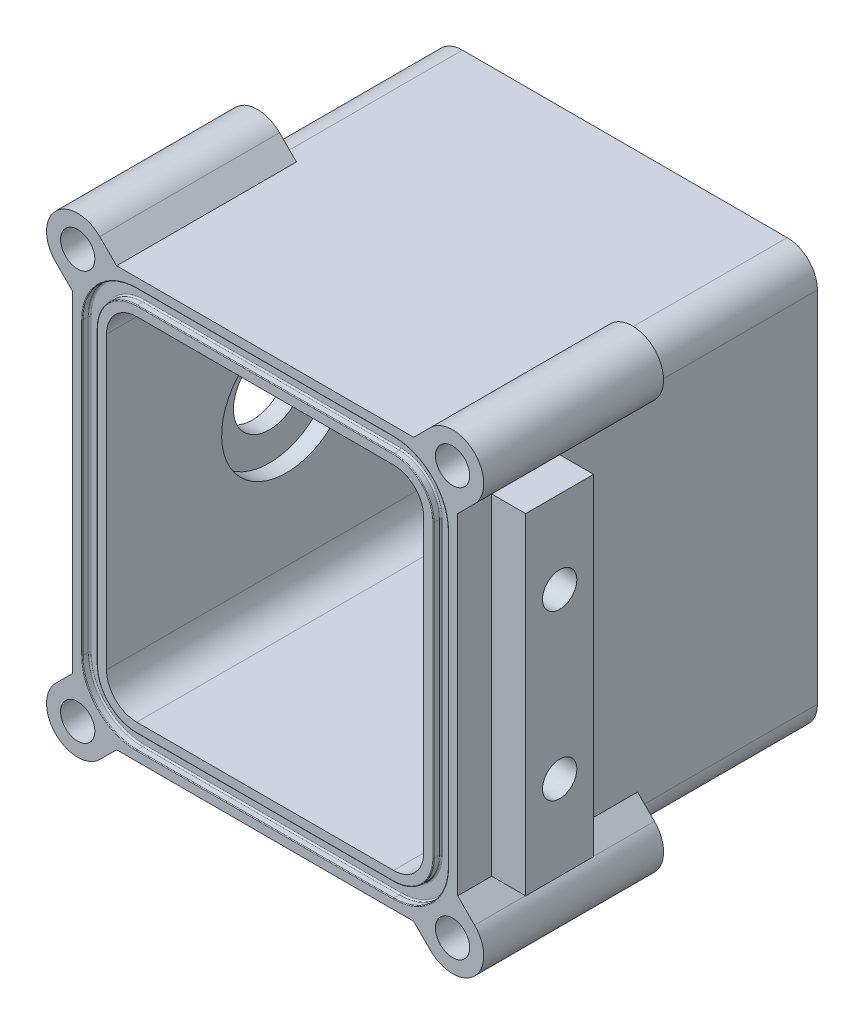
SolidWorks part; units mm, degrees
material "ABS"
ref_plane "X-Y Datum" through (0, 0, 0) normal (0, 0, 1) x (1, 0, 0)
ref_plane "X-Z Datum" through (0, 0, 0) normal (0, 1, 0) x (1, 0, 0)
ref_plane "Y-Z Datum" through (0, 0, 0) normal (1, 0, 0) x (0, 0, -1)
sketch "Sketch1" plane through (0, 0, 0) normal (0, 0, 1) x (1, 0, 0)
  line L0 (-34, -37) -> (-34, -16.68)
  line L1 (34, 37) -> (-34, 37)
  line L2 (34, 37) -> (34, -37)
  line L3 (34, -37) -> (-34, -37)
  line L5 (34, 37) -> (-34, -37) construction
  line L6 (34, -37) -> (-34, 37) construction
  line L7 (55.1739, 0) -> (-55.1739, 0) construction
  line L8 (-34, 37) -> (-34, 16.68)
  line L9 (-34, 16.68) -> (-34, -16.68)
  arc A0 (-34, -16.68) -> (-34, 16.68) centre (-14.8444, 0) cw construction
  point P0 (0, 0)
  dimension "D2" = 25.4
  dimension "D1" = 74
  dimension "D3" = 20.32
  dimension "D4" = 68
extrude "Boss-Extrude1" add sketch "Sketch1" along normal mid plane 63.5
shell "Shell1" thickness 6 removed face at (0, 0, 31.75)
fillet "Fillet1" radius 5.334 8 edges at (34, 37, 0) (34, -37, 0) (-34, -37, 0) (-34, 37, 0) (28, 31, 3) (28, -31, 3) (-28, -31, 3) (-28, 31, 3)
sketch "Sketch2" plane through (0, 0, 31.75) normal (0, 0, 1) x (1, 0, 0)
  line L21 (32.2827, -25.666) -> (32.2827, 25.666)
  line L22 (22.666, 35.2827) -> (-22.666, 35.2827)
  line L23 (-32.2827, 25.666) -> (-32.2827, -25.666)
  line L24 (-22.666, -35.2827) -> (22.666, -35.2827)
  line L25 (31, -25.666) -> (31, 25.666)
  line L26 (-22.666, -34) -> (22.666, -34)
  line L27 (-31, 25.666) -> (-31, -25.666)
  line L28 (22.666, 34) -> (-22.666, 34)
  line L29 (31, -25.666) -> (31, 25.666) construction
  line L30 (-22.666, -34) -> (22.666, -34) construction
  line L31 (-31, 25.666) -> (-31, -25.666) construction
  line L32 (22.666, 34) -> (-22.666, 34) construction
  line L33 (-29.7173, 25.666) -> (-29.7173, -25.666)
  line L34 (-22.666, -32.7173) -> (22.666, -32.7173)
  line L35 (29.7173, -25.666) -> (29.7173, 25.666)
  line L36 (22.666, 32.7173) -> (-22.666, 32.7173)
  arc A15 (32.2827, 25.666) -> (22.666, 35.2827) centre (22.666, 25.666) ccw
  arc A16 (-22.666, 35.2827) -> (-32.2827, 25.666) centre (-22.666, 25.666) ccw
  arc A17 (-32.2827, -25.666) -> (-22.666, -35.2827) centre (-22.666, -25.666) ccw
  arc A18 (22.666, -35.2827) -> (32.2827, -25.666) centre (22.666, -25.666) ccw
  arc A19 (31, 25.666) -> (22.666, 34) centre (22.666, 25.666) ccw
  arc A20 (22.666, -34) -> (31, -25.666) centre (22.666, -25.666) ccw
  arc A21 (-31, -25.666) -> (-22.666, -34) centre (-22.666, -25.666) ccw
  arc A22 (-22.666, 34) -> (-31, 25.666) centre (-22.666, 25.666) ccw
  arc A23 (31, 25.666) -> (22.666, 34) centre (22.666, 25.666) ccw construction
  arc A24 (22.666, -34) -> (31, -25.666) centre (22.666, -25.666) ccw construction
  arc A25 (-31, -25.666) -> (-22.666, -34) centre (-22.666, -25.666) ccw construction
  arc A26 (-22.666, 34) -> (-31, 25.666) centre (-22.666, 25.666) ccw construction
  arc A27 (-22.666, 32.7173) -> (-29.7173, 25.666) centre (-22.666, 25.666) ccw
  arc A28 (-29.7173, -25.666) -> (-22.666, -32.7173) centre (-22.666, -25.666) ccw
  arc A29 (22.666, -32.7173) -> (29.7173, -25.666) centre (22.666, -25.666) ccw
  arc A30 (29.7173, 25.666) -> (22.666, 32.7173) centre (22.666, 25.666) ccw
  dimension "D4" = 7.0513
  dimension "D5" = 2.5654
  dimension "D1" = 3
  dimension "D2" = 1.2827
  dimension "D3" = 1.2827
extrude "Cut-Extrude1" cut sketch "Sketch2" against normal blind 1.2954
fillet "Fillet2" radius 0.254 16 edges at (27.652, -30.652, 30.4546) (0, -32.7173, 30.4546) (-27.652, -30.652, 30.4546) (-29.7173, 0, 30.4546) (-27.652, 30.652, 30.4546) (0, 32.7173, 30.4546) (27.652, 30.652, 30.4546) (-29.466, 32.466, 30.4546) (0, 35.2827, 30.4546) (29.466, 32.466, 30.4546) (32.2827, 0, 30.4546) (29.466, -32.466, 30.4546) (0, -35.2827, 30.4546) (-29.466, -32.466, 30.4546) (29.7173, 0, 30.4546) (-32.2827, 0, 30.4546)
fillet "Fillet3" radius 0.127 16 edges at (-29.466, -32.466, 31.75) (-32.2827, 0, 31.75) (-29.466, 32.466, 31.75) (0, 35.2827, 31.75) (29.466, 32.466, 31.75) (32.2827, 0, 31.75) (29.466, -32.466, 31.75) (-27.652, -30.652, 31.75) (-29.7173, 0, 31.75) (-27.652, 30.652, 31.75) (0, 32.7173, 31.75) (27.652, 30.652, 31.75) (29.7173, 0, 31.75) (27.652, -30.652, 31.75) (0, -35.2827, 31.75) (0, -32.7173, 31.75)
sketch "Sketch3" plane through (0, 0, 31.75) normal (0, 0, 1) x (1, 0, 0)
  line L0 (22.666, -25.666) -> (37.7124, -40.7124) construction
  line L1 (29.2023, -39.9805) -> (26.2218, -37)
  line L2 (-28.666, -37) -> (28.666, -37) construction
  line L3 (22.666, -25.666) -> (0, 0)
  line L5 (34, -29.2218) -> (36.9805, -32.2023)
  line L6 (34, -31.666) -> (34, 31.666) construction
  arc A0 (22.666, -35.4097) -> (32.4097, -25.666) centre (22.666, -25.666) ccw construction
  arc A1 (22.666, -35.4097) -> (32.4097, -25.666) centre (22.666, -25.666) ccw
  circle A2 centre (33.0914, -36.0914) radius 3.025
  circle A3 centre (33.0914, -36.0914) radius 5.5
  point P7 (29.5558, -32.5558)
  arc M9 (32.4097, -25.666) -> (22.666, -35.4097) centre (22.666, -25.666) cw
  line M14 (-28.666, -37) -> (28.666, -37)
  arc M15 (28.666, -37) -> (34, -31.666) centre (28.666, -31.666) ccw
  line M16 (34, -31.666) -> (34, 31.666)
  dimension "D1" = 6.05
  dimension "D3" = 11
  dimension "D2" = 5
extrude "Boss-Extrude2" add sketch "Sketch3" against normal blind 31.75 contours L0 A2 A3 M15 M14 | A2 L0 A3 M16 M15 | L0 A2 M15 | L0 A2 M15 | A2 L0 M15 | A3 M14 | A3 M16 | A1 L0 A2 A3 M15 M16 | L0 A2 M15 | L0 A3 A2 M9 M14 M15 region at (32.0118, -32.0896, 31.75) region at (29.0896, -35.0118, 31.75) region at (32.4421, -34.0333, 31.75) region at (31.0333, -35.4421, 31.75) region at (34.789, -30.4552, 31.75) region at (36.5269, -35.0577, 31.75) region at (32.0577, -39.5269, 31.75) region at (27.4552, -37.789, 31.75) region at (34.5525, -35.5923, 31.75) region at (32.5923, -37.5525, 31.75)
sketch "Sketch4" plane through (0, 0, 31.75) normal (0, 0, 1) x (1, 0, 0)
  circle A0 centre (33.0914, -36.0914) radius 3.025 construction
  circle A1 centre (33.0914, -36.0914) radius 3.025
  dimension "D1" = 6.05
extrude "Cut-Extrude2" cut sketch "Sketch4" against normal blind 9
mirror "Mirror1" about plane through (0, 0, 0) normal (0, 1, 0) of "Cut-Extrude2", "Boss-Extrude2"
mirror "Mirror2" about plane through (0, 0, 0) normal (1, 0, 0) of "Mirror1", "Cut-Extrude2", "Boss-Extrude2"
sketch "Sketch8" plane through (-34, 0, 0) normal (-1, 0, 0) x (0, 0, 1)
  line L0 (19.75, 29.2218) -> (19.75, -29.2218) construction
  line L11 (25.75, 29.2218) -> (25.75, -29.2218)
  line L12 (0, 29.2218) -> (31.75, 29.2218) construction
  line L13 (0, -29.2218) -> (31.75, -29.2218) construction
  line L14 (25.75, 29.2218) -> (13.75, 29.2218)
  line L15 (13.75, 29.2218) -> (13.75, -29.2218)
  line L16 (13.75, -29.2218) -> (25.75, -29.2218)
  line L17 (13.75, 0) -> (25.75, 0) construction
  line L18 (25.75, 29.2218) -> (13.75, 29.2218)
  line L19 (25.75, -29.2218) -> (13.75, -29.2218)
  point P0 (0, 0)
  line M1 (31.75, 29.2218) -> (0, 29.2218)
  line M7 (0, -29.2218) -> (31.75, -29.2218)
extrude "Boss-Extrude3" add sketch "Sketch8" along normal blind 6 contours L15 L11 M1 M7 region at (-34, 0, 19.75)
sketch "Sketch12" plane through (-40, 0, 0) normal (-1, 0, 0) x (0, 0, 1)
  line L0 (19.75, 29.2218) -> (19.75, -29.2218) construction
  line L1 (25.75, 29.2218) -> (13.75, 29.2218) construction
  line L2 (13.75, -29.2218) -> (25.75, -29.2218) construction
  line L3 (13.75, 0) -> (25.75, 0) construction
  line L4 (13.75, 29.2218) -> (13.75, -29.2218) construction
  line L5 (25.75, 29.2218) -> (25.75, -29.2218) construction
  circle A0 centre (19.75, 14.6168) radius 3.025
  circle A1 centre (19.75, -14.3392) radius 3.025
  dimension "D1" = 14.605
  dimension "D3" = 6.05
  dimension "D2" = 6.05
extrude "Cut-Extrude6" cut sketch "Sketch12" against normal blind 9
sketch "Sketch13" plane through (-34, 0, 0) normal (-1, 0, 0) x (0, 0, 1)
  line L0 (-31.75, 0) -> (31.75, 0) construction
  line L3 (-31.75, 31.666) -> (-31.75, -31.666) construction
  line L4 (31.75, 29.2218) -> (31.75, -29.2218) construction
  circle A0 centre (0, 0) radius 6.35
  dimension "D2" = 12.7
extrude "Cut-Extrude10" cut sketch "Sketch13" against normal blind 6 contours A0 | A0 region at (-34, 0, 0)
sketch "Sketch16" plane through (-28, 0, 0) normal (1, 0, 0) x (0, 0, -1)
  circle A0 centre (0, 0) radius 11.43
  dimension "D1" = 22.86
extrude "Cut-Extrude14" cut sketch "Sketch16" against normal blind 3
mirror "Mirror5" about plane through (0, 0, 0) normal (1, 0, 0) of "Boss-Extrude3"
mirror "Mirror6" about plane through (0, 0, 0) normal (1, 0, 0) of "Cut-Extrude6"
